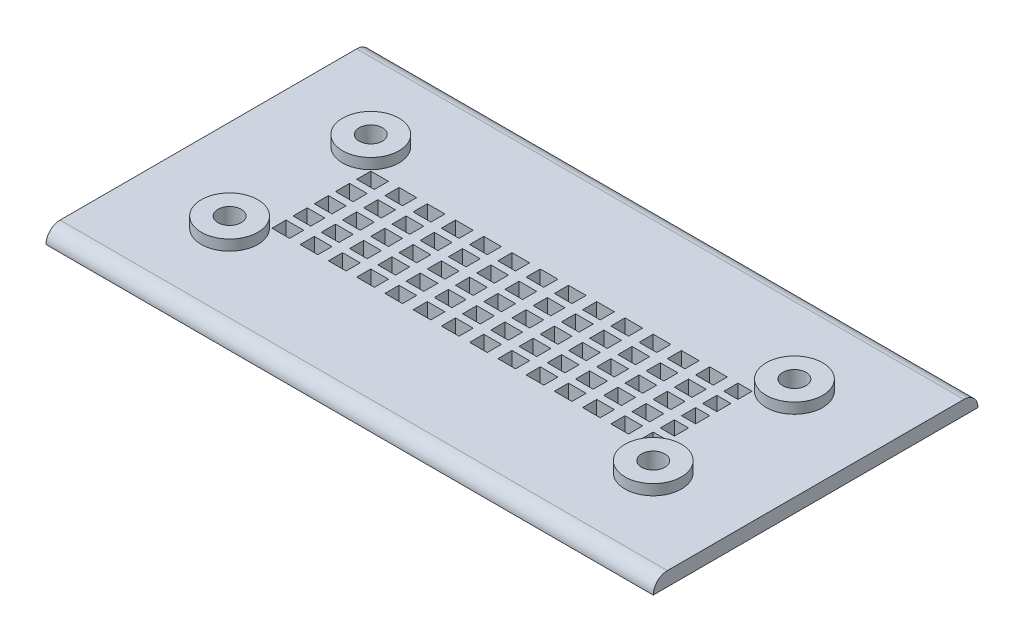
SolidWorks part; units mm, degrees
ref_plane "Front Plane" through (0, 0, 0) normal (0, 0, 1) x (1, 0, 0)
ref_plane "Top Plane" through (0, 0, 0) normal (0, 1, 0) x (1, 0, 0)
ref_plane "Right Plane" through (0, 0, 0) normal (1, 0, 0) x (0, 0, -1)
sketch "Sketch1" plane through (0, 0, 0) normal (0, 1, 0) x (1, 0, 0)
  line L1 (43, -23) -> (-43, -23)
  line L2 (43, -23) -> (43, 23)
  line L3 (43, 23) -> (-43, 23)
  line L4 (-43, -23) -> (-43, 23)
  line L5 (43, -23) -> (-43, 23) construction
  line L6 (43, 23) -> (-43, -23) construction
  point P0 (0, 0)
  dimension "D1" = 86
  dimension "D2" = 46
extrude "Boss-Extrude1" add sketch "Sketch1" along normal blind 2
sketch "Sketch2" plane through (0, 2, 0) normal (0, 1, 0) x (1, 0, 0)
  line L1 (27, -7) -> (-27, -7)
  line L2 (27, -7) -> (27, 7)
  line L3 (27, 7) -> (-27, 7)
  line L4 (-27, -7) -> (-27, 7)
  line L5 (27, -7) -> (-27, 7) construction
  line L6 (27, 7) -> (-27, -7) construction
  point P0 (0, 0)
  dimension "D1" = 14
  dimension "D2" = 54
extrude "Cut-Extrude1" cut sketch "Sketch2" against normal through all
sketch "Sketch4" plane through (0, 2, 0) normal (0, 1, 0) x (1, 0, 0)
  line L0 (27, 7) -> (-27, 7) construction
  line L1 (-27, 7) -> (-27, -7) construction
  line L2 (0, 23) -> (0, 0) construction
  line L3 (43, 23) -> (-43, 23) construction
  line L4 (0, 0) -> (-43, 0) construction
  line L5 (-43, 23) -> (-43, -23) construction
  circle A0 centre (-30, 10) radius 4
  circle A1 centre (-30, -10) radius 4
  circle A2 centre (30, -10) radius 4
  circle A3 centre (30, 10) radius 4
  dimension "D1" = 8
  dimension "D2" = 3
  dimension "D3" = 3
sketch "Sketch3" plane through (0, 2, 0) normal (0, 1, 0) x (1, 0, 0)
  line L0 (27, 7) -> (-27, 7) construction
  line L1 (-27, 7) -> (-27, -7) construction
  line L2 (0, 23) -> (0, 0) construction
  line L3 (43, 23) -> (-43, 23) construction
  line L4 (0, 0) -> (-43, 0) construction
  line L5 (-43, 23) -> (-43, -23) construction
  circle A0 centre (-30, 10) radius 1.65
  circle A1 centre (30, 10) radius 1.65
  circle A2 centre (30, -10) radius 1.65
  circle A3 centre (-30, -10) radius 1.65
  dimension "D1" = 3.3
  dimension "D2" = 3
  dimension "D3" = 3
extrude "Boss-Extrude2" add sketch "Sketch4" along normal blind 1.5
extrude "Cut-Extrude2" cut sketch "Sketch3" along normal up to surface (1.5 mm away) and the other way blind 10 up to face at (-30, 3.5, 6)
sketch "Sketch5" plane through (0, 0, 0) normal (0, -1, 0) x (1, 0, 0)
  line L0 (-37, -17) -> (-37, 17)
  line L1 (-37, 17) -> (37, 17)
  line L2 (37, 17) -> (37, -17)
  line L3 (37, -17) -> (-37, -17)
  line L4 (-35, -15) -> (-35, 15)
  line L5 (-35, 15) -> (35, 15)
  line L6 (35, 15) -> (35, -15)
  line L7 (35, -15) -> (-35, -15)
  line L8 (-27, -7) -> (-27, 7) construction
  line L9 (-27, 7) -> (27, 7) construction
  line L10 (27, 7) -> (27, -7) construction
  line L11 (27, -7) -> (-27, -7) construction
  dimension "D1" = 2
  dimension "D2" = 2
  dimension "D3" = 2
  dimension "D4" = 2
  dimension "D5" = 8
  dimension "D6" = 8
  dimension "D7" = 8
  dimension "D8" = 8
extrude "Cut-Extrude3" cut sketch "Sketch5" against normal blind 10 draft 45
fillet "Fillet1" radius 2 1 edges at (0, 2, -23) type face fillet first side face at (0, 1, -23) second side face at (30, 2, 14)
fillet "Fillet2" radius 2 1 edges at (0, 2, 23) type face fillet first side face at (30, 2, 14) second side face at (0, 1, 23)
sketch "Sketch6" plane through (0, 0, 0) normal (0, -1, 0) x (1, 0, 0)
  line L0 (-27, 7) -> (27, 7) construction
  line L1 (-24.5, 7) -> (-23, 7)
  line L2 (-24.5, 7) -> (-24.5, 5)
  line L3 (-24.5, -7) -> (-23, -7)
  line L4 (-23, 7) -> (-23, 5)
  line L5 (27, -7) -> (-27, -7) construction
  line L6 (-27, -7) -> (-27, 7) construction
  line L7 (-27, 5) -> (-24.5, 5)
  line L8 (-27, 5) -> (-27, 4)
  line L9 (-27, 4) -> (-24.5, 4)
  line L10 (-24.5, 1) -> (-24.5, -1)
  line L11 (-24.5, 0) -> (-27, 0) construction
  line L12 (-27, -1) -> (-24.5, -1)
  line L13 (-27, -2) -> (-24.5, -2)
  line L14 (-27, -4) -> (-24.5, -4)
  line L15 (-27, -5) -> (-24.5, -5)
  line L16 (-27, 2) -> (-24.5, 2)
  line L17 (-27, 2) -> (-27, 1)
  line L18 (-27, 1) -> (-24.5, 1)
  line L19 (-24.5, -2) -> (-24.5, -4)
  line L20 (-27, -2) -> (-27, -1)
  line L21 (-27, -5) -> (-27, -4)
  line L22 (-24.5, 4) -> (-24.5, 2)
  line L23 (-24.5, -5) -> (-24.5, -7)
  line L24 (-20.5, 7) -> (-19, 7)
  line L25 (-20.5, 7) -> (-20.5, 5)
  line L26 (-20.5, -7) -> (-19, -7)
  line L27 (-19, 7) -> (-19, 5)
  line L28 (-23, 5) -> (-20.5, 5)
  line L29 (-23, 1) -> (-23, -1)
  line L30 (-23, 4) -> (-20.5, 4)
  line L31 (-20.5, 1) -> (-20.5, -1)
  line L32 (-23, -1) -> (-20.5, -1)
  line L33 (-23, -2) -> (-20.5, -2)
  line L34 (-23, -4) -> (-20.5, -4)
  line L35 (-23, -5) -> (-20.5, -5)
  line L36 (-23, 2) -> (-20.5, 2)
  line L37 (-23, -2) -> (-23, -4)
  line L38 (-23, 1) -> (-20.5, 1)
  line L39 (-20.5, -2) -> (-20.5, -4)
  line L40 (-23, -5) -> (-23, -7)
  line L41 (-19, -5) -> (-19, -7)
  line L42 (-20.5, 4) -> (-20.5, 2)
  line L43 (-20.5, -5) -> (-20.5, -7)
  line L44 (-20.5, 0) -> (-23, 0) construction
  line L45 (-16.5, 7) -> (-15, 7)
  line L46 (-16.5, 7) -> (-16.5, 5)
  line L47 (-16.5, -7) -> (-15, -7)
  line L48 (-15, 7) -> (-15, 5)
  line L49 (-19, 5) -> (-16.5, 5)
  line L50 (-15, 4) -> (-15, 2)
  line L51 (-19, 4) -> (-16.5, 4)
  line L52 (-16.5, 1) -> (-16.5, -1)
  line L53 (-19, -1) -> (-16.5, -1)
  line L54 (-19, -2) -> (-16.5, -2)
  line L55 (-19, -4) -> (-16.5, -4)
  line L56 (-19, -5) -> (-16.5, -5)
  line L57 (-19, 2) -> (-16.5, 2)
  line L58 (-19, 4) -> (-19, 2)
  line L59 (-19, 1) -> (-16.5, 1)
  line L60 (-16.5, -2) -> (-16.5, -4)
  line L61 (-19, 1) -> (-19, -1)
  line L62 (-19, -2) -> (-19, -4)
  line L63 (-16.5, 4) -> (-16.5, 2)
  line L64 (-16.5, -5) -> (-16.5, -7)
  line L65 (-16.5, 0) -> (-19, 0) construction
  line L66 (-12.5, 7) -> (-11, 7)
  line L67 (-12.5, 7) -> (-12.5, 5)
  line L68 (-12.5, -7) -> (-11, -7)
  line L69 (-11, 7) -> (-11, 5)
  line L70 (-15, 5) -> (-12.5, 5)
  line L71 (-15, 1) -> (-15, -1)
  line L72 (-15, 4) -> (-12.5, 4)
  line L73 (-12.5, 1) -> (-12.5, -1)
  line L74 (-15, -1) -> (-12.5, -1)
  line L75 (-15, -2) -> (-12.5, -2)
  line L76 (-15, -4) -> (-12.5, -4)
  line L77 (-15, -5) -> (-12.5, -5)
  line L78 (-15, 2) -> (-12.5, 2)
  line L79 (-15, -2) -> (-15, -4)
  line L80 (-15, 1) -> (-12.5, 1)
  line L81 (-12.5, -2) -> (-12.5, -4)
  line L82 (-15, -5) -> (-15, -7)
  line L83 (-11, -5) -> (-11, -7)
  line L84 (-12.5, 4) -> (-12.5, 2)
  line L85 (-12.5, -5) -> (-12.5, -7)
  line L86 (-12.5, 0) -> (-15, 0) construction
  line L87 (-8.5, 7) -> (-7, 7)
  line L88 (-8.5, 7) -> (-8.5, 5)
  line L89 (-8.5, -7) -> (-7, -7)
  line L90 (-7, 7) -> (-7, 5)
  line L91 (-11, 5) -> (-8.5, 5)
  line L92 (5, 4) -> (5, 2)
  line L93 (-11, 4) -> (-8.5, 4)
  line L94 (-8.5, 1) -> (-8.5, -1)
  line L95 (-11, -1) -> (-8.5, -1)
  line L96 (-11, -2) -> (-8.5, -2)
  line L97 (-11, -4) -> (-8.5, -4)
  line L98 (-11, -5) -> (-8.5, -5)
  line L99 (-11, 2) -> (-8.5, 2)
  line L100 (-3, 4) -> (-3, 2)
  line L101 (-11, 1) -> (-8.5, 1)
  line L102 (-8.5, -2) -> (-8.5, -4)
  line L103 (-11, 1) -> (-11, -1)
  line L104 (-7, -2) -> (-7, -4)
  line L105 (-8.5, 4) -> (-8.5, 2)
  line L106 (-8.5, -5) -> (-8.5, -7)
  line L107 (-8.5, 0) -> (-11, 0) construction
  line L108 (-4.5, 7) -> (-3, 7)
  line L109 (-4.5, 7) -> (-4.5, 5)
  line L110 (-4.5, -7) -> (-3, -7)
  line L111 (-3, 7) -> (-3, 5)
  line L112 (-7, 5) -> (-4.5, 5)
  line L113 (9, 4) -> (9, 2)
  line L114 (-7, 4) -> (-4.5, 4)
  line L115 (-4.5, 1) -> (-4.5, -1)
  line L116 (-7, -1) -> (-4.5, -1)
  line L117 (-7, -2) -> (-4.5, -2)
  line L118 (-7, -4) -> (-4.5, -4)
  line L119 (-7, -5) -> (-4.5, -5)
  line L120 (-7, 2) -> (-4.5, 2)
  line L121 (-7, 4) -> (-7, 2)
  line L122 (-7, 1) -> (-4.5, 1)
  line L123 (-4.5, -2) -> (-4.5, -4)
  line L124 (-7, 1) -> (-7, -1)
  line L125 (-11, -2) -> (-11, -4)
  line L126 (-4.5, 4) -> (-4.5, 2)
  line L127 (-4.5, -5) -> (-4.5, -7)
  line L128 (-4.5, 0) -> (-7, 0) construction
  line L129 (-0.5, 7) -> (1, 7)
  line L130 (-0.5, 7) -> (-0.5, 5)
  line L131 (-0.5, -7) -> (1, -7)
  line L132 (1, 7) -> (1, 5)
  line L133 (-3, 5) -> (-0.5, 5)
  line L134 (13, 4) -> (13, 2)
  line L135 (-3, 4) -> (-0.5, 4)
  line L136 (-0.5, 1) -> (-0.5, -1)
  line L137 (-3, -1) -> (-0.5, -1)
  line L138 (-3, -2) -> (-0.5, -2)
  line L139 (-3, -4) -> (-0.5, -4)
  line L140 (-3, -5) -> (-0.5, -5)
  line L141 (-3, 2) -> (-0.5, 2)
  line L142 (-11, 4) -> (-11, 2)
  line L143 (-3, 1) -> (-0.5, 1)
  line L144 (-0.5, -2) -> (-0.5, -4)
  line L145 (-3, 1) -> (-3, -1)
  line L146 (17, 4) -> (17, 2)
  line L147 (-0.5, 4) -> (-0.5, 2)
  line L148 (-0.5, -5) -> (-0.5, -7)
  line L149 (-0.5, 0) -> (-3, 0) construction
  line L150 (3.5, 7) -> (5, 7)
  line L151 (3.5, 7) -> (3.5, 5)
  line L152 (3.5, -7) -> (5, -7)
  line L153 (5, 7) -> (5, 5)
  line L154 (1, 5) -> (3.5, 5)
  line L156 (1, 4) -> (3.5, 4)
  line L157 (3.5, 1) -> (3.5, -1)
  line L158 (1, -1) -> (3.5, -1)
  line L159 (1, -2) -> (3.5, -2)
  line L160 (1, -4) -> (3.5, -4)
  line L161 (1, -5) -> (3.5, -5)
  line L162 (1, 2) -> (3.5, 2)
  line L163 (13, 1) -> (13, -1)
  line L164 (1, 1) -> (3.5, 1)
  line L165 (3.5, -2) -> (3.5, -4)
  line L166 (1, -5) -> (1, -7)
  line L167 (5, -5) -> (5, -7)
  line L168 (3.5, 4) -> (3.5, 2)
  line L169 (3.5, -5) -> (3.5, -7)
  line L170 (3.5, 0) -> (1, 0) construction
  line L171 (7.5, 7) -> (9, 7)
  line L172 (7.5, 7) -> (7.5, 5)
  line L173 (7.5, -7) -> (9, -7)
  line L174 (9, 7) -> (9, 5)
  line L175 (5, 5) -> (7.5, 5)
  line L176 (9, 1) -> (9, -1)
  line L177 (5, 4) -> (7.5, 4)
  line L178 (7.5, 1) -> (7.5, -1)
  line L179 (5, -1) -> (7.5, -1)
  line L180 (5, -2) -> (7.5, -2)
  line L181 (5, -4) -> (7.5, -4)
  line L182 (5, -5) -> (7.5, -5)
  line L183 (5, 2) -> (7.5, 2)
  line L184 (17, 1) -> (17, -1)
  line L185 (5, 1) -> (7.5, 1)
  line L186 (7.5, -2) -> (7.5, -4)
  line L187 (1, -2) -> (1, -4)
  line L188 (9, -5) -> (9, -7)
  line L189 (7.5, 4) -> (7.5, 2)
  line L190 (7.5, -5) -> (7.5, -7)
  line L191 (7.5, 0) -> (5, 0) construction
  line L192 (11.5, 7) -> (13, 7)
  line L193 (11.5, 7) -> (11.5, 5)
  line L194 (11.5, -7) -> (13, -7)
  line L195 (13, 7) -> (13, 5)
  line L196 (9, 5) -> (11.5, 5)
  line L197 (5, 1) -> (5, -1)
  line L198 (9, 4) -> (11.5, 4)
  line L199 (11.5, 1) -> (11.5, -1)
  line L200 (9, -1) -> (11.5, -1)
  line L201 (9, -2) -> (11.5, -2)
  line L202 (9, -4) -> (11.5, -4)
  line L203 (9, -5) -> (11.5, -5)
  line L204 (9, 2) -> (11.5, 2)
  line L205 (21, 1) -> (21, -1)
  line L206 (9, 1) -> (11.5, 1)
  line L207 (11.5, -2) -> (11.5, -4)
  line L208 (5, -2) -> (5, -4)
  line L209 (13, -5) -> (13, -7)
  line L210 (11.5, 4) -> (11.5, 2)
  line L211 (11.5, -5) -> (11.5, -7)
  line L212 (11.5, 0) -> (9, 0) construction
  line L213 (15.5, 7) -> (17, 7)
  line L214 (15.5, 7) -> (15.5, 5)
  line L215 (15.5, -7) -> (17, -7)
  line L216 (17, 7) -> (17, 5)
  line L217 (13, 5) -> (15.5, 5)
  line L218 (1, 1) -> (1, -1)
  line L219 (13, 4) -> (15.5, 4)
  line L220 (15.5, 1) -> (15.5, -1)
  line L221 (13, -1) -> (15.5, -1)
  line L222 (13, -2) -> (15.5, -2)
  line L223 (13, -4) -> (15.5, -4)
  line L224 (13, -5) -> (15.5, -5)
  line L225 (13, 2) -> (15.5, 2)
  line L226 (21, -2) -> (21, -4)
  line L227 (13, 1) -> (15.5, 1)
  line L228 (15.5, -2) -> (15.5, -4)
  line L229 (9, -2) -> (9, -4)
  line L230 (17, -5) -> (17, -7)
  line L231 (15.5, 4) -> (15.5, 2)
  line L232 (15.5, -5) -> (15.5, -7)
  line L233 (15.5, 0) -> (13, 0) construction
  line L234 (19.5, 7) -> (21, 7)
  line L235 (19.5, 7) -> (19.5, 5)
  line L236 (19.5, -7) -> (21, -7)
  line L237 (21, 7) -> (21, 5)
  line L238 (17, 5) -> (19.5, 5)
  line L239 (17, -2) -> (17, -4)
  line L240 (17, 4) -> (19.5, 4)
  line L241 (19.5, 1) -> (19.5, -1)
  line L242 (17, -1) -> (19.5, -1)
  line L243 (17, -2) -> (19.5, -2)
  line L244 (17, -4) -> (19.5, -4)
  line L245 (17, -5) -> (19.5, -5)
  line L246 (17, 2) -> (19.5, 2)
  line L247 (13, -2) -> (13, -4)
  line L248 (17, 1) -> (19.5, 1)
  line L249 (19.5, -2) -> (19.5, -4)
  line L250 (21, -5) -> (21, -7)
  line L251 (25, 5) -> (27, 5)
  line L252 (19.5, 4) -> (19.5, 2)
  line L253 (19.5, -5) -> (19.5, -7)
  line L254 (19.5, 0) -> (17, 0) construction
  line L255 (23.5, 7) -> (25, 7)
  line L256 (23.5, 7) -> (23.5, 5)
  line L257 (23.5, -7) -> (25, -7)
  line L258 (25, 7) -> (25, 5)
  line L259 (21, 5) -> (23.5, 5)
  line L260 (25, 2) -> (27, 2)
  line L261 (21, 4) -> (23.5, 4)
  line L262 (23.5, 1) -> (23.5, -1)
  line L263 (21, -1) -> (23.5, -1)
  line L264 (21, -2) -> (23.5, -2)
  line L265 (21, -4) -> (23.5, -4)
  line L266 (21, -5) -> (23.5, -5)
  line L267 (21, 2) -> (23.5, 2)
  line L268 (25, -1) -> (27, -1)
  line L269 (21, 1) -> (23.5, 1)
  line L270 (23.5, -2) -> (23.5, -4)
  line L271 (25, -4) -> (27, -4)
  line L272 (25, 4) -> (25, 2)
  line L273 (23.5, 4) -> (23.5, 2)
  line L274 (23.5, -5) -> (23.5, -7)
  line L275 (23.5, 0) -> (21, 0) construction
  line L276 (-23, 4) -> (-23, 2)
  line L277 (-23, 5) -> (-23, 4) [skipped]
  line L278 (-23, 2) -> (-23, 1) [skipped]
  line L279 (-23, -2) -> (-23, -1) [skipped]
  line L280 (-23, -5) -> (-23, -4) [skipped]
  line L281 (-19, -5) -> (-19, -4) [skipped]
  line L282 (-19, -2) -> (-19, -1) [skipped]
  line L283 (-19, 2) -> (-19, 1) [skipped]
  line L284 (-19, 5) -> (-19, 4) [skipped]
  line L285 (-15, 5) -> (-15, 4) [skipped]
  line L286 (-15, 2) -> (-15, 1) [skipped]
  line L287 (-15, -2) -> (-15, -1) [skipped]
  line L288 (-15, -5) -> (-15, -4) [skipped]
  line L289 (-11, -5) -> (-11, -4) [skipped]
  line L290 (-7, -5) -> (-7, -4) [skipped]
  line L291 (-7, -5) -> (-7, -7)
  line L292 (-3, -5) -> (-3, -4) [skipped]
  line L293 (-3, -5) -> (-3, -7)
  line L294 (-3, -2) -> (-3, -4)
  line L295 (-3, -2) -> (-3, -1) [skipped]
  line L296 (-7, -2) -> (-7, -1) [skipped]
  line L297 (-11, -2) -> (-11, -1) [skipped]
  line L298 (-11, 2) -> (-11, 1) [skipped]
  line L299 (-7, 2) -> (-7, 1) [skipped]
  line L300 (-3, 2) -> (-3, 1) [skipped]
  line L301 (-3, 5) -> (-3, 4) [skipped]
  line L302 (-7, 5) -> (-7, 4) [skipped]
  line L303 (-11, 5) -> (-11, 4) [skipped]
  line L304 (5, 5) -> (5, 4) [skipped]
  line L305 (9, 5) -> (9, 4) [skipped]
  line L306 (13, 5) -> (13, 4) [skipped]
  line L307 (17, 5) -> (17, 4) [skipped]
  line L308 (21, 4) -> (21, 2)
  line L309 (21, 5) -> (21, 4) [skipped]
  line L310 (9, 2) -> (9, 1) [skipped]
  line L311 (5, 2) -> (5, 1) [skipped]
  line L312 (1, 2) -> (1, 1) [skipped]
  line L313 (13, 2) -> (13, 1) [skipped]
  line L314 (17, 2) -> (17, 1) [skipped]
  line L315 (21, 2) -> (21, 1) [skipped]
  line L316 (21, -2) -> (21, -1) [skipped]
  line L317 (17, -2) -> (17, -1) [skipped]
  line L318 (13, -2) -> (13, -1) [skipped]
  line L319 (9, -2) -> (9, -1) [skipped]
  line L320 (5, -2) -> (5, -1) [skipped]
  line L321 (1, -2) -> (1, -1) [skipped]
  line L322 (1, -5) -> (1, -4) [skipped]
  line L323 (5, -5) -> (5, -4) [skipped]
  line L324 (9, -5) -> (9, -4) [skipped]
  line L325 (13, -5) -> (13, -4) [skipped]
  line L326 (17, -5) -> (17, -4) [skipped]
  line L327 (21, -5) -> (21, -4) [skipped]
  line L328 (27, 7) -> (27, -7) construction
  line L329 (27, 5) -> (27, 4)
  line L330 (27, 4) -> (25, 4)
  line L331 (1, 4) -> (1, 2)
  line L332 (27, 2) -> (27, 1)
  line L333 (27, 1) -> (25, 1)
  line L335 (27, -1) -> (27, -2)
  line L336 (27, -2) -> (25, -2)
  line L338 (27, -4) -> (27, -5)
  line L339 (27, -5) -> (25, -5)
  line L341 (25, 1) -> (25, -1)
  line L342 (25, -2) -> (25, -4)
  line L343 (25, -5) -> (25, -7)
  line L344 (1, 5) -> (1, 4) [skipped]
  dimension "D1" = 2.5
  dimension "D2" = 1
  dimension "D3" = 2
  dimension "D4" = 2
  dimension "D5" = 1
  dimension "D6" = 1.5
  dimension "D7" = 13
extrude "Grid" add sketch "Sketch6" against normal up to surface (2 mm away) up to face at (30, 2, 14)
